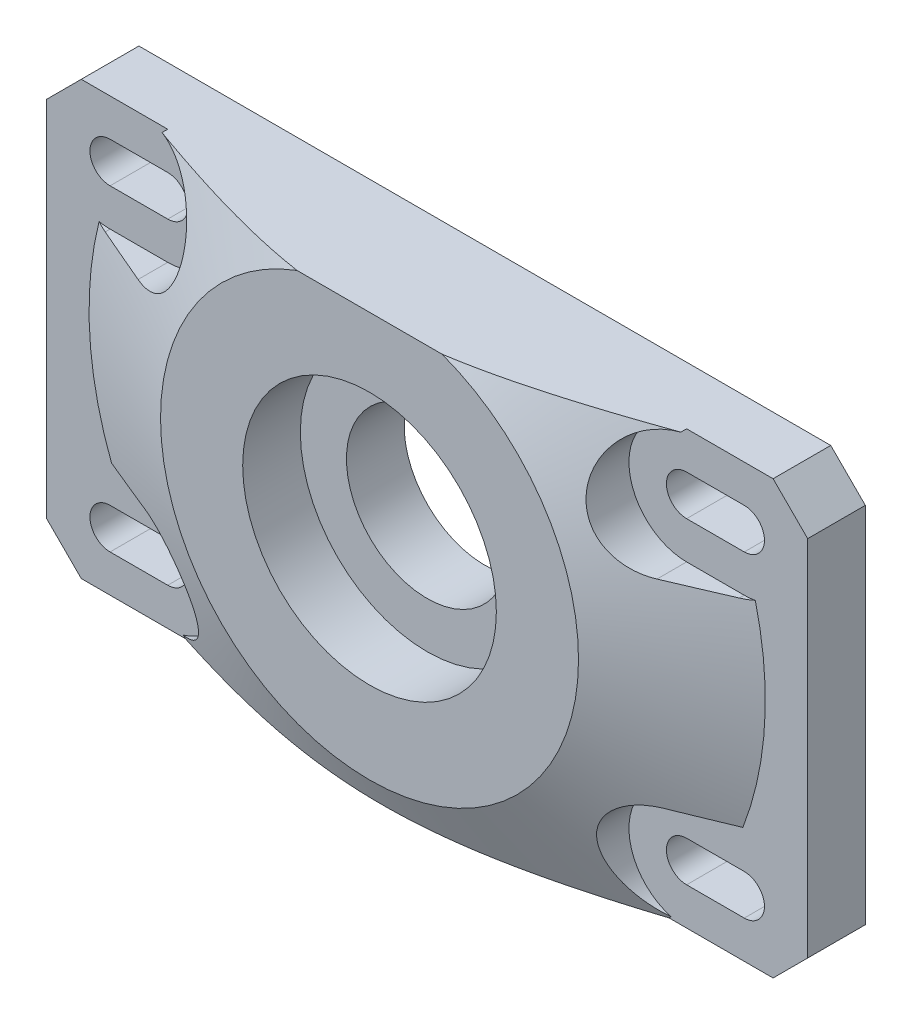
SolidWorks part; units mm, degrees
material "ABS"
ref_plane "Front Plane" through (0, 0, 0) normal (0, 0, 1) x (1, 0, 0)
ref_plane "Top Plane" through (0, 0, 0) normal (0, 1, 0) x (1, 0, 0)
ref_plane "Right Plane" through (0, 0, 0) normal (1, 0, 0) x (0, 0, -1)
sketch "Sketch1" plane through (0, 0, 0) normal (0, 0, 1) x (1, 0, 0)
  line L0 (-27.5, 13.75) -> (-22.5, 13.75) construction
  line L1 (30, 18.75) -> (-30, 18.75)
  line L2 (33, 15.75) -> (33, -15.75)
  line L3 (30, -18.75) -> (-30, -18.75)
  line L4 (-33, 15.75) -> (-33, -15.75)
  line L5 (33, 18.75) -> (-33, -18.75) construction
  line L6 (33, -18.75) -> (-33, 18.75) construction
  line L7 (-27.5, 15.5) -> (-22.5, 15.5)
  line L8 (-27.5, 12) -> (-22.5, 12)
  line L9 (22.5, 13.75) -> (27.5, 13.75) construction
  line L10 (22.5, 15.5) -> (27.5, 15.5)
  line L11 (22.5, 12) -> (27.5, 12)
  line L12 (-27.5, -13.75) -> (-22.5, -13.75) construction
  line L13 (-27.5, -12) -> (-22.5, -12)
  line L14 (-27.5, -15.5) -> (-22.5, -15.5)
  line L15 (22.5, -13.75) -> (27.5, -13.75) construction
  line L16 (22.5, -12) -> (27.5, -12)
  line L17 (22.5, -15.5) -> (27.5, -15.5)
  line L18 (-27.5, -13.75) -> (-27.5, 13.75) construction
  line L19 (-22.5, -13.75) -> (-22.5, 13.75) construction
  line L20 (22.5, -13.75) -> (22.5, 13.75) construction
  line L21 (27.5, 13.75) -> (27.5, -13.75) construction
  line L22 (0, 0) -> (0, 1.75) construction
  line L23 (-30, 18.75) -> (-33, 15.75)
  line L24 (-30, -18.75) -> (-33, -15.75)
  line L25 (33, -15.75) -> (30, -18.75)
  line L26 (33, 15.75) -> (30, 18.75)
  arc A1 (-27.5, 15.5) -> (-27.5, 12) centre (-27.5, 13.75) ccw
  arc A2 (-22.5, 12) -> (-22.5, 15.5) centre (-22.5, 13.75) ccw
  arc A3 (22.5, 15.5) -> (22.5, 12) centre (22.5, 13.75) ccw
  arc A4 (27.5, 12) -> (27.5, 15.5) centre (27.5, 13.75) ccw
  arc A5 (-27.5, -12) -> (-27.5, -15.5) centre (-27.5, -13.75) ccw
  arc A6 (-22.5, -15.5) -> (-22.5, -12) centre (-22.5, -13.75) ccw
  arc A7 (22.5, -12) -> (22.5, -15.5) centre (22.5, -13.75) ccw
  arc A8 (27.5, -15.5) -> (27.5, -12) centre (27.5, -13.75) ccw
  circle A9 centre (0, 1.75) radius 7
  point P0 (0, 0)
  point P10 (-25, 13.75)
  point P15 (25, 13.75)
  point P22 (-25, -13.75)
  point P29 (25, -13.75)
  dimension "D3" = 13.75
  dimension "D10" = 1.75
  dimension "D11" = 1.75
  dimension "D12" = 1.75
  dimension "D13" = 1.75
  dimension "D8" = 1.75
  dimension "D14" = 14
  dimension "D1" = 37.5
  dimension "D2" = 66
  dimension "D4" = 5
  dimension "D5" = 5
  dimension "D6" = 5.5
  dimension "D7" = 50
  dimension "D9" = 27.5
extrude "Boss-Extrude1" add sketch "Sketch1" along normal blind 5
sketch "Sketch2" plane through (0, 0, 5) normal (0, 0, 1) x (1, 0, 0)
  circle A0 centre (0, 1.75) radius 11
  circle A1 centre (0, 1.75) radius 18.125
  dimension "D1" = 36.25
  dimension "D2" = 22
extrude "Boss-Extrude2" add sketch "Sketch2" along normal blind 5
ref_plane "Plane1" through (0, 1.75, 0) normal (0, 1, 0) x (1, 0, 0)
ref_axis "Axis1" through (0, 1.75, 5) along (0, 0, -1)
chamfer "Chamfer1" distance 11.2 distance2 5 1 edges at (0, -16.375, 5) first distance on face at (0, 0.2375, 5)
sketch "Sketch4" plane through (0, 0, 5) normal (0, 0, 1) x (1, 0, 0)
  line L0 (-27.5, 13.75) -> (-22.5, 13.75) construction
  line L1 (-27.5, 18.75) -> (-22.5, 18.75)
  line L2 (-27.5, 8.75) -> (-22.5, 8.75)
  line L3 (-27.5, -13.75) -> (-22.5, -13.75) construction
  line L4 (-27.5, -8.75) -> (-22.5, -8.75)
  line L5 (-27.5, -18.75) -> (-22.5, -18.75)
  line L6 (27.5, -13.75) -> (22.5, -13.75) construction
  line L7 (27.5, -18.75) -> (22.5, -18.75)
  line L8 (27.5, -8.75) -> (22.5, -8.75)
  line L9 (27.5, 13.75) -> (22.5, 13.75) construction
  line L10 (27.5, 8.75) -> (22.5, 8.75)
  line L11 (27.5, 18.75) -> (22.5, 18.75)
  arc A0 (-27.5, 18.75) -> (-27.5, 8.75) centre (-27.5, 13.75) ccw
  arc A1 (-22.5, 8.75) -> (-22.5, 18.75) centre (-22.5, 13.75) ccw
  arc A2 (-27.5, -8.75) -> (-27.5, -18.75) centre (-27.5, -13.75) ccw
  arc A3 (-22.5, -18.75) -> (-22.5, -8.75) centre (-22.5, -13.75) ccw
  arc A4 (27.5, -18.75) -> (27.5, -8.75) centre (27.5, -13.75) ccw
  arc A5 (22.5, -8.75) -> (22.5, -18.75) centre (22.5, -13.75) ccw
  arc A6 (27.5, 8.75) -> (27.5, 18.75) centre (27.5, 13.75) ccw
  arc A7 (22.5, 18.75) -> (22.5, 8.75) centre (22.5, 13.75) ccw
  point P2 (-25, -13.75)
  point P6 (-25, 13.75)
  point P15 (25, -13.75)
  point P24 (25, 13.75)
  dimension "D4" = 5
  dimension "D6" = 5
  dimension "D8" = 5
  dimension "D1" = 10
  dimension "D2" = 5
  dimension "D3" = 5
  dimension "D5" = 5
  dimension "D7" = 5
extrude "Cut-Extrude1" cut sketch "Sketch4" along normal through all
sketch "Sketch5" plane through (0, 0, 0) normal (0, 0, -1) x (-1, 0, 0)
  line L0 (-6.2861, 18.75) -> (6.2861, 18.75)
  arc A0 (-6.2861, 18.75) -> (6.2861, 18.75) centre (0, 1.75) cw
  arc A1 (6.2861, 18.75) -> (-6.2861, 18.75) centre (0, 1.75) ccw construction
extrude "Cut-Extrude2" cut sketch "Sketch5" against normal through all
